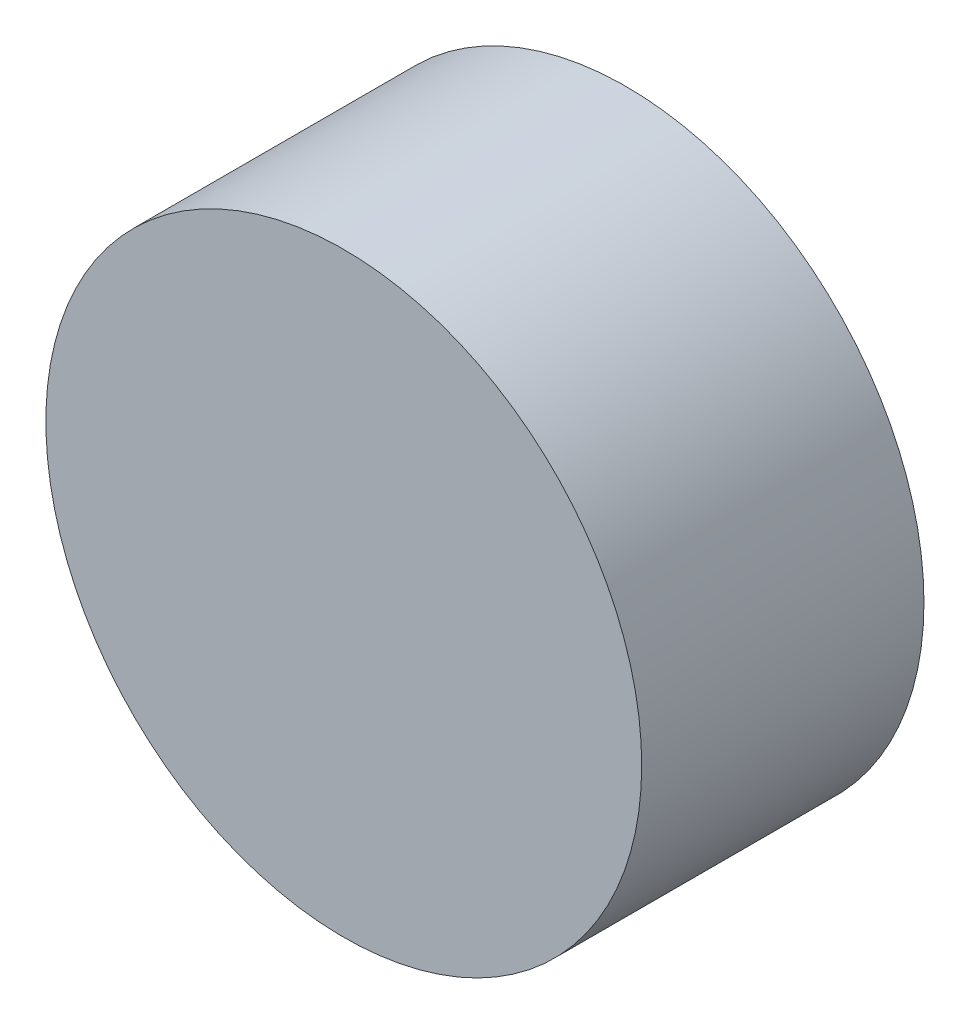
SolidWorks part; units mm, degrees
ref_plane "Plano frontal" through (0, 0, 0) normal (0, 0, 1) x (1, 0, 0)
ref_plane "Plano superior" through (0, 0, 0) normal (0, 1, 0) x (1, 0, 0)
ref_plane "Plano direito" through (0, 0, 0) normal (1, 0, 0) x (0, 0, -1)
sketch "Esboço1" plane through (0, 0, 0) normal (0, 0, 1) x (1, 0, 0)
  circle A0 centre (0, 0) radius 38
  dimension "D1" = 76
extrude "Ressalto-extrusão1" add sketch "Esboço1" along normal blind 36
